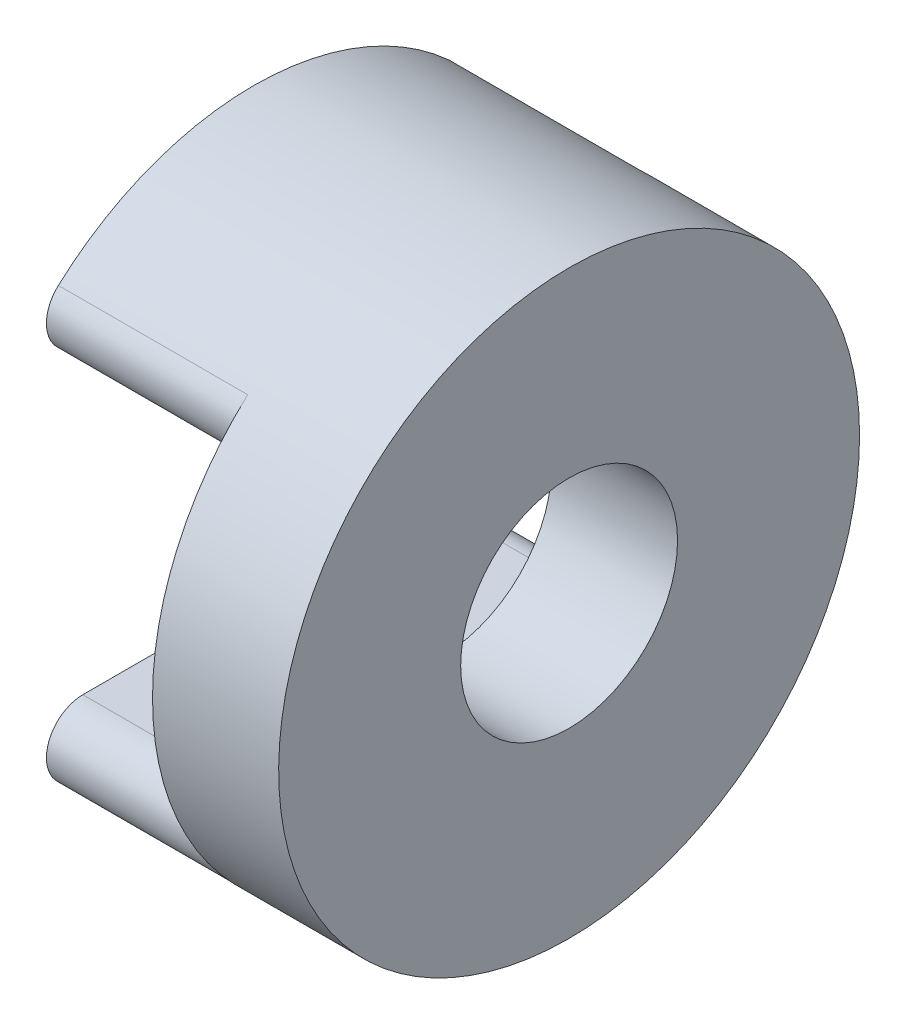
SolidWorks part; units mm, degrees
ref_plane "Front Plane" through (0, 0, 0) normal (0, 0, 1) x (1, 0, 0)
ref_plane "Top Plane" through (0, 0, 0) normal (0, 1, 0) x (1, 0, 0)
ref_plane "Right Plane" through (0, 0, 0) normal (1, 0, 0) x (0, 0, -1)
sketch "Sketch1" plane through (0, 0, 0) normal (1, 0, 0) x (0, 0, -1)
  circle A0 centre (0, 0) radius 23.9375
  circle A1 centre (0, 0) radius 8.9375
  dimension "D1" = 17.875
  dimension "D2" = 15
extrude "Boss-Extrude1" add sketch "Sketch1" along normal blind 26
sketch "Sketch2" plane through (0, 0, 0) normal (0, 0, 1) x (1, 0, 0)
  line L1 (0, 12.5) -> (15.6043, 12.5)
  line L2 (0, 12.5) -> (0, -12.5)
  line L3 (0, -12.5) -> (15.6043, -12.5)
  line L4 (15.6043, 12.5) -> (15.6043, -12.5)
  dimension "D1" = 25
extrude "Cut-Extrude1" cut sketch "Sketch2" against normal through all both and the other way through all
fillet "Fillet1" radius 3 4 edges at (7.8021, 12.5, 20.4146) (7.8021, -12.5, 20.4146) (7.8021, -12.5, -20.4146) (7.8021, 12.5, -20.4146)
